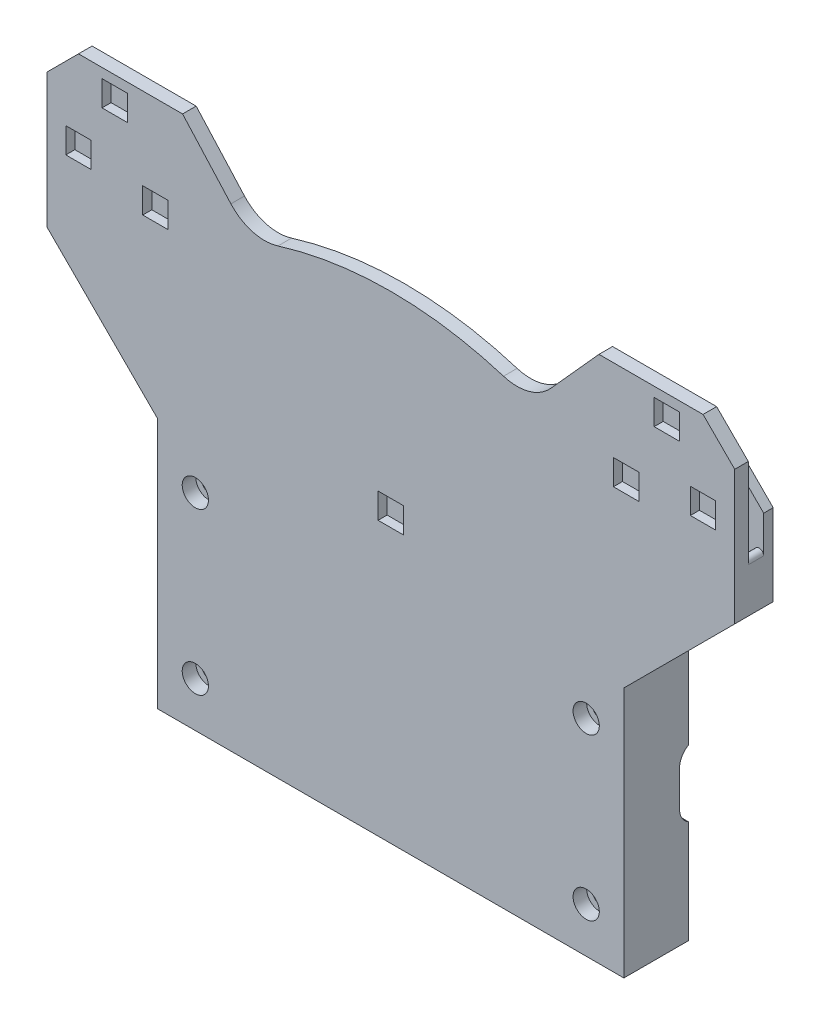
SolidWorks part; units mm, degrees
ref_plane "Front Plane" through (0, 0, 0) normal (0, 0, 1) x (1, 0, 0)
ref_plane "Top Plane" through (0, 0, 0) normal (0, 1, 0) x (1, 0, 0)
ref_plane "Right Plane" through (0, 0, 0) normal (1, 0, 0) x (0, 0, -1)
sketch "Sketch1" plane through (0, 0, 0) normal (0, 0, 1) x (1, 0, 0)
  circle A0 centre (43.18, -17.78) radius 3.5
  circle A1 centre (43.18, -17.78) radius 1.5 construction
  circle A2 centre (43.18, -17.78) radius 1.5
  circle A3 centre (43.18, 17.78) radius 1.5 construction
  circle A4 centre (-43.18, 17.78) radius 1.5 construction
  circle A5 centre (-43.18, -17.78) radius 1.5 construction
  circle A6 centre (43.18, 17.78) radius 1.5
  circle A7 centre (-43.18, 17.78) radius 1.5
  circle A8 centre (-43.18, -17.78) radius 1.5
  circle A9 centre (43.18, 17.78) radius 3.5
  circle A10 centre (-43.18, -17.78) radius 3.5
  circle A11 centre (-43.18, 17.78) radius 3.5
  dimension "D1" = 7
extrude "Boss-Extrude1" add sketch "Sketch1" along normal blind 5
sketch "Sketch2" plane through (0, 0, 5) normal (0, 0, 1) x (1, 0, 0)
  line L9 (-51.5, 27.75) -> (-51.5, -27.75)
  line L10 (-51.5, -27.75) -> (51.5, -27.75)
  line L11 (51.5, -27.75) -> (51.5, 27.75)
  line L12 (51.5, 27.75) -> (-51.5, 27.75)
  line L13 (-51.5, 27.75) -> (-51.5, -27.75)
  line L14 (-51.5, -27.75) -> (51.5, -27.75)
  line L15 (51.5, -27.75) -> (51.5, 27.75)
  line L16 (51.5, 27.75) -> (-51.5, 27.75)
  circle A0 centre (43.18, -17.78) radius 1.5 construction
  circle A1 centre (43.18, -17.78) radius 1.5
  circle A2 centre (-43.18, -17.78) radius 1.5 construction
  circle A3 centre (-43.18, -17.78) radius 1.5
  circle A4 centre (43.18, 17.78) radius 1.5 construction
  circle A5 centre (43.18, 17.78) radius 1.5
  circle A6 centre (-43.18, 17.78) radius 1.5 construction
  circle A7 centre (-43.18, 17.78) radius 1.5
  dimension "D1" = 3
extrude "Boss-Extrude2" add sketch "Sketch2" along normal blind 2
sketch "Sketch4" plane through (0, 0, 7) normal (0, 0, 1) x (1, 0, 0)
  line L0 (76, 68.9071) -> (76, 118.9) construction
  line L1 (76, 68.9071) -> (76, 118.9)
  line L2 (-76, 118.9) -> (-76, 68.9071) construction
  line L3 (-76, 118.9) -> (-76, 68.9071)
  line L4 (76, 68.9071) -> (76, -27.75)
  line L5 (76, -27.75) -> (-76, -27.75)
  line L6 (-76, -27.75) -> (-76, 68.9071)
  line L7 (-51.5, -27.75) -> (51.5, -27.75) construction
  line L8 (76, 88.84) -> (46, 88.84)
  line L9 (46, 88.84) -> (28, 68.84)
  line L10 (0, 0) -> (0, 120.911) construction
  line L11 (-46, 88.84) -> (-28, 68.84)
  line L12 (-76, 88.84) -> (-46, 88.84)
  line L13 (51.5, -27.75) -> (51.5, 27.75) construction
  line L14 (51.5, 27.75) -> (-51.5, 27.75) construction
  line L15 (-51.5, 27.75) -> (-51.5, -27.75) construction
  line L16 (51.5, -27.75) -> (51.5, 27.75)
  line L17 (51.5, 27.75) -> (-51.5, 27.75)
  line L18 (-51.5, 27.75) -> (-51.5, -27.75)
  circle A0 centre (-69, 70.9) radius 1.5 construction
  circle A1 centre (-69, 70.9) radius 1.5
  circle A2 centre (-52, 67.9) radius 1.5 construction
  circle A3 centre (-52, 67.9) radius 1.5
  circle A4 centre (69, 70.9) radius 1.5 construction
  circle A5 centre (69, 70.9) radius 1.5
  circle A6 centre (52, 67.9) radius 1.5 construction
  circle A7 centre (52, 67.9) radius 1.5
  arc A8 (41.0357, 62.5736) -> (-41.0357, 62.5736) centre (0, -6.1) ccw construction
  arc A9 (41.0357, 62.5736) -> (-41.0357, 62.5736) centre (0, -6.1) ccw
  circle A10 centre (61, 83.9) radius 1.5 construction
  circle A11 centre (61, 83.9) radius 1.5
  circle A12 centre (-61, 83.9) radius 1.5 construction
  circle A13 centre (-61, 83.9) radius 1.5
  circle A14 centre (0, 35.482) radius 1.5 construction
  circle A15 centre (0, 35.482) radius 1.5
  dimension "D1" = 30
  dimension "D2" = 20
  dimension "D3" = 18
extrude "Boss-Extrude3" add sketch "Sketch4" against normal up to surface (2 mm away)
sketch "Sketch6" plane through (0, 0, 5) normal (0, 0, -1) x (-1, 0, 0)
  line L0 (49, -25.25) -> (49, 25.25)
  line L1 (49, 25.25) -> (-49, 25.25)
  line L2 (-49, 25.25) -> (-49, -25.25)
  line L3 (-49, -25.25) -> (49, -25.25)
  line L4 (48.5, -24.75) -> (48.5, 24.75)
  line L5 (48.5, 24.75) -> (-48.5, 24.75)
  line L6 (-48.5, 24.75) -> (-48.5, -24.75)
  line L7 (-48.5, -24.75) -> (48.5, -24.75)
  line L8 (48.5, -24.75) -> (48.5, 24.75) construction
  line L9 (48.5, 24.75) -> (-48.5, 24.75) construction
  line L10 (-48.5, 24.75) -> (-48.5, -24.75) construction
  line L11 (-48.5, -24.75) -> (48.5, -24.75) construction
  line L12 (-51.5, -27.75) -> (51.5, -27.75)
  line L13 (51.5, -27.75) -> (51.5, 27.75)
  line L14 (51.5, 27.75) -> (-51.5, 27.75)
  line L15 (-51.5, 27.75) -> (-51.5, -27.75)
  dimension "D1" = 0
  dimension "D2" = 0.5
  dimension "D3" = 2.5
extrude "Boss-Extrude4" add sketch "Sketch6" along normal up to surface (6.6 mm away)
sketch "Sketch7" plane through (0, 0, 5) normal (0, 0, -1) x (-1, 0, 0)
  line L0 (-51.5, 27.75) -> (-76, 52.25)
  line L1 (-76, -27.75) -> (-76, 88.84) construction
  line L2 (-76, 52.25) -> (-76, -27.75)
  line L3 (-76, -27.75) -> (-51.5, -27.75)
  line L4 (-51.5, -27.75) -> (-51.5, 27.75)
  line L5 (51.5, 27.75) -> (76, 52.25)
  line L6 (76, -27.75) -> (76, 88.84) construction
  line L7 (76, 52.25) -> (76, -27.75)
  line L8 (76, -27.75) -> (51.5, -27.75)
  line L9 (51.5, -27.75) -> (51.5, 27.75)
  line L10 (-76, 52.25) -> (76, 52.25) construction
  dimension "D1" = 45
extrude "Cut-Extrude1" cut sketch "Sketch7" against normal blind 10
sketch "Sketch9" plane through (0, 0, 5) normal (0, 0, -1) x (-1, 0, 0)
  line L0 (76.3, 68.9071) -> (76.3, 118.9831)
  line L1 (76.3, 118.9831) -> (70.3, 128.9831)
  line L2 (70.3, 128.9831) -> (70.3, 208.8169)
  line L3 (70.3, 208.8169) -> (76.3, 218.8169)
  line L4 (76.3, 218.8169) -> (76.3, 288.5517)
  line L5 (-76.3, 288.5517) -> (-76.3, 218.8169)
  line L6 (-76.3, 218.8169) -> (-70.3, 208.8169)
  line L7 (-70.3, 208.8169) -> (-70.3, 128.9831)
  line L8 (-70.3, 128.9831) -> (-76.3, 118.9831)
  line L9 (-76.3, 118.9831) -> (-76.3, 68.9071)
  line L10 (76, 68.9071) -> (76, 118.9)
  line L11 (76, 118.9) -> (70, 128.9)
  line L12 (70, 128.9) -> (70, 208.9)
  line L13 (70, 208.9) -> (76, 218.9)
  line L14 (76, 218.9) -> (76, 288.4236)
  line L15 (-76, 288.4236) -> (-76, 218.9)
  line L16 (-76, 218.9) -> (-70, 208.9)
  line L17 (-70, 208.9) -> (-70, 128.9)
  line L18 (-70, 128.9) -> (-76, 118.9)
  line L19 (-76, 118.9) -> (-76, 68.9071)
  line L20 (76, 68.9071) -> (76, 118.9) construction
  line L21 (76, 118.9) -> (70, 128.9) construction
  line L22 (70, 128.9) -> (70, 208.9) construction
  line L23 (70, 208.9) -> (76, 218.9) construction
  line L24 (76, 218.9) -> (76, 288.4236) construction
  line L25 (-76, 288.4236) -> (-76, 218.9) construction
  line L26 (-76, 218.9) -> (-70, 208.9) construction
  line L27 (-70, 208.9) -> (-70, 128.9) construction
  line L28 (-70, 128.9) -> (-76, 118.9) construction
  line L29 (-76, 118.9) -> (-76, 68.9071) construction
  line L39 (-76, 88.84) -> (-76, 52.25)
  line L40 (-76, 52.25) -> (-51.5, 27.75)
  line L41 (-51.5, 27.75) -> (51.5, 27.75)
  line L42 (51.5, 27.75) -> (76, 52.25)
  line L43 (76, 52.25) -> (76, 88.84)
  line L44 (76, 88.84) -> (46, 88.84)
  line L45 (46, 88.84) -> (28, 68.84)
  line L46 (-28, 68.84) -> (-46, 88.84)
  line L47 (-46, 88.84) -> (-76, 88.84)
  line L48 (-76, 88.84) -> (-76, 52.25)
  line L49 (-76, 52.25) -> (-51.5, 27.75)
  line L50 (-51.5, 27.75) -> (51.5, 27.75)
  line L51 (51.5, 27.75) -> (76, 52.25)
  line L52 (76, 52.25) -> (76, 88.84)
  line L53 (76, 88.84) -> (46, 88.84)
  line L54 (46, 88.84) -> (28, 68.84)
  line L55 (-28, 68.84) -> (-46, 88.84)
  line L56 (-46, 88.84) -> (-76, 88.84)
  arc A1 (-66.1471, 58.6082) -> (-40.9121, 62.298) centre (-65, 138.9) ccw
  arc A2 (40.9121, 62.298) -> (-40.9121, 62.298) centre (0, -6.1) ccw
  arc A3 (40.9121, 62.298) -> (66.1471, 58.6082) centre (65, 138.9) ccw
  arc A4 (66.1471, 58.6082) -> (76.3, 68.9071) centre (66, 68.9071) ccw
  arc A5 (76.3, 288.5517) -> (-76.3, 288.5517) centre (0, 208.9) ccw
  arc A6 (-76.3, 68.9071) -> (-66.1471, 58.6082) centre (-66, 68.9071) ccw
  arc A7 (41.0357, 62.5736) -> (-41.0357, 62.5736) centre (0, -6.1) ccw
  arc A8 (41.0357, 62.5736) -> (66.1429, 58.9082) centre (65, 138.9) ccw
  arc A9 (66.1429, 58.9082) -> (76, 68.9071) centre (66, 68.9071) ccw
  arc A10 (76, 288.4236) -> (-76, 288.4236) centre (0, 208.9) ccw
  arc A11 (-76, 68.9071) -> (-66.1429, 58.9082) centre (-66, 68.9071) ccw
  arc A12 (-66.1429, 58.9082) -> (-41.0357, 62.5736) centre (-65, 138.9) ccw
  arc A13 (41.0357, 62.5736) -> (-41.0357, 62.5736) centre (0, -6.1) ccw construction
  arc A14 (41.0357, 62.5736) -> (66.1429, 58.9082) centre (65, 138.9) ccw construction
  arc A15 (66.1429, 58.9082) -> (76, 68.9071) centre (66, 68.9071) ccw construction
  arc A16 (76, 288.4236) -> (-76, 288.4236) centre (0, 208.9) ccw construction
  arc A17 (-76, 68.9071) -> (-66.1429, 58.9082) centre (-66, 68.9071) ccw construction
  arc A18 (-66.1429, 58.9082) -> (-41.0357, 62.5736) centre (-65, 138.9) ccw construction
  circle A19 centre (0, 35.482) radius 1.5 construction
  arc A20 (28, 68.84) -> (-28, 68.84) centre (0, -6.1) ccw
  arc A21 (28, 68.84) -> (-28, 68.84) centre (0, -6.1) ccw
  circle A22 centre (0, 35.482) radius 1.5
  circle M29 centre (0, 35.482) radius 1.5
  line M35 (-76, 52.25) -> (-51.5, 27.75)
  line M36 (-51.5, 27.75) -> (51.5, 27.75)
  line M37 (51.5, 27.75) -> (76, 52.25)
  line M38 (76, 52.25) -> (76, 88.84)
  dimension "D1" = 0
  dimension "D2" = 0.3
  dimension "D3" = 0
extrude "Boss-Extrude5" add sketch "Sketch9" along normal up to surface (3 mm away) contours A6 L48 A4 A3 A2 A1 M35 M36 M37 M38 M29
sketch "Sketch10" plane through (0, 0, 2) normal (0, 0, -1) x (-1, 0, 0)
  line L1 (-5.1061, 39.5578) -> (-4.2, 38.4952)
  line L2 (-4.2, 38.4952) -> (-4.2, 35.482)
  line L3 (4.2, 35.482) -> (4.2, 38.5758)
  line L4 (4.2, 38.5758) -> (5.1906, 39.5664)
  line L5 (-51.5, 27.75) -> (-76, 52.25) construction
  line L6 (-51.5, 27.75) -> (-76, 52.25)
  line L7 (51.5, 27.75) -> (-51.5, 27.75) construction
  line L8 (51.5, 27.75) -> (-51.5, 27.75)
  line L9 (76, 52.25) -> (51.5, 27.75) construction
  line L10 (76, 52.25) -> (51.5, 27.75)
  line L11 (-76, 52.25) -> (-76, 66.4394) construction
  line L12 (-76, 52.25) -> (-76, 66.4394)
  line L13 (76, 66.4394) -> (76, 52.25) construction
  line L14 (76, 66.4394) -> (76, 52.25)
  line L15 (76, 66.4394) -> (76, 77.25)
  line L16 (76, 66.4394) -> (76, 88.84) construction
  line L17 (76, 77.25) -> (-76, 77.25)
  line L18 (-76, 66.4394) -> (-76, 88.84) construction
  line L19 (-76, 77.25) -> (-76, 66.4394)
  line L21 (50.7778, 80.9023) -> (60.602, 79.9199)
  line L22 (61.398, 87.8801) -> (51.4846, 88.8715)
  line L23 (51.4846, 88.8715) -> (50.4999, 90.0749)
  line L24 (26.5818, 132.9378) -> (26.1966, 134.4398)
  line L25 (26.1966, 134.4398) -> (28.693, 139.542)
  line L26 (21.507, 143.058) -> (18.9712, 137.8751)
  line L27 (18.9712, 137.8751) -> (17.5004, 137.3707)
  line L28 (-17.5883, 137.3382) -> (-19.0106, 137.9557)
  line L29 (-19.0106, 137.9557) -> (-21.507, 143.058)
  line L30 (-28.693, 139.542) -> (-26.1571, 134.3592)
  line L31 (-26.1571, 134.3592) -> (-26.6615, 132.8884)
  line L32 (-50.5, 89.9811) -> (-51.5738, 88.8626)
  line L33 (-51.5738, 88.8626) -> (-61.398, 87.8801)
  line L34 (-60.602, 79.9199) -> (-50.6885, 80.9112)
  line L35 (-50.6885, 80.9112) -> (-49.4851, 79.9266)
  line L36 (-5.0061, 39.7487) -> (-4, 38.5689)
  line L37 (-4, 38.5689) -> (-4, 35.482)
  line L38 (4, 35.482) -> (4, 38.6587)
  line L39 (4, 38.6587) -> (5.0995, 39.7581)
  line L40 (49.5037, 80.0185) -> (50.7778, 80.9023)
  line L41 (50.7778, 80.9023) -> (60.602, 79.9199) construction
  line L42 (61.398, 87.8801) -> (51.4846, 88.8715) construction
  line L43 (51.4846, 88.8715) -> (50.4999, 90.0749) construction
  line L44 (26.5818, 132.9378) -> (26.1966, 134.4398) construction
  line L45 (26.1966, 134.4398) -> (28.693, 139.542) construction
  line L46 (21.507, 143.058) -> (18.9712, 137.8751) construction
  line L47 (18.9712, 137.8751) -> (17.5004, 137.3707) construction
  line L48 (-17.5883, 137.3382) -> (-19.0106, 137.9557) construction
  line L49 (-19.0106, 137.9557) -> (-21.507, 143.058) construction
  line L50 (-28.693, 139.542) -> (-26.1571, 134.3592) construction
  line L51 (-26.1571, 134.3592) -> (-26.6615, 132.8884) construction
  line L52 (-50.5, 89.9811) -> (-51.5738, 88.8626) construction
  line L53 (-51.5738, 88.8626) -> (-61.398, 87.8801) construction
  line L54 (-60.602, 79.9199) -> (-50.6885, 80.9112) construction
  line L55 (-50.6885, 80.9112) -> (-49.4851, 79.9266) construction
  line L56 (-5.0061, 39.7487) -> (-4, 38.5689) construction
  line L57 (-4, 38.5689) -> (-4, 35.482) construction
  line L58 (4, 35.482) -> (4, 38.6587) construction
  line L59 (4, 38.6587) -> (5.0995, 39.7581) construction
  line L60 (49.5037, 80.0185) -> (50.7778, 80.9023) construction
  arc A0 (-4, 35.482) -> (4, 35.482) centre (0, 35.482) ccw construction
  arc A1 (-4, 35.482) -> (4, 35.482) centre (0, 35.482) ccw construction
  arc A2 (-4.2, 35.482) -> (4.2, 35.482) centre (0, 35.482) ccw
  arc A3 (-49.6811, 79.8867) -> (-5.1061, 39.5578) centre (0, 90) ccw
  arc A4 (5.1906, 39.5664) -> (49.6998, 79.979) centre (0, 90) ccw
  circle A5 centre (-69, 70.9) radius 1.5 construction
  circle A6 centre (-69, 70.9) radius 1.5
  circle A7 centre (-52, 67.9) radius 1.5 construction
  circle A8 centre (-52, 67.9) radius 1.5
  circle A9 centre (52, 67.9) radius 1.5 construction
  arc A10 (61.398, 87.8801) -> (60.602, 79.9199) centre (61, 83.9) ccw
  arc A11 (50.4999, 90.0749) -> (26.5818, 132.9378) centre (0, 90) ccw
  arc A12 (21.507, 143.058) -> (28.693, 139.542) centre (25.1, 141.3) ccw
  arc A13 (17.5004, 137.3707) -> (-17.5883, 137.3382) centre (0, 90) ccw
  arc A14 (-28.693, 139.542) -> (-21.507, 143.058) centre (-25.1, 141.3) ccw
  arc A15 (-26.6615, 132.8884) -> (-50.5, 89.9811) centre (0, 90) ccw
  arc A16 (-60.602, 79.9199) -> (-61.398, 87.8801) centre (-61, 83.9) ccw
  arc A17 (-49.4851, 79.9266) -> (-5.0061, 39.7487) centre (0, 90) ccw
  arc A18 (4, 35.482) -> (-4, 35.482) centre (0, 35.482) ccw
  arc A19 (5.0995, 39.7581) -> (49.5037, 80.0185) centre (0, 90) ccw
  arc A20 (61.398, 87.8801) -> (60.602, 79.9199) centre (61, 83.9) ccw construction
  arc A21 (50.4999, 90.0749) -> (26.5818, 132.9378) centre (0, 90) ccw construction
  arc A22 (21.507, 143.058) -> (28.693, 139.542) centre (25.1, 141.3) ccw construction
  arc A23 (17.5004, 137.3707) -> (-17.5883, 137.3382) centre (0, 90) ccw construction
  arc A24 (-28.693, 139.542) -> (-21.507, 143.058) centre (-25.1, 141.3) ccw construction
  arc A25 (-26.6615, 132.8884) -> (-50.5, 89.9811) centre (0, 90) ccw construction
  arc A26 (-60.602, 79.9199) -> (-61.398, 87.8801) centre (-61, 83.9) ccw construction
  arc A27 (-49.4851, 79.9266) -> (-5.0061, 39.7487) centre (0, 90) ccw construction
  arc A28 (4, 35.482) -> (-4, 35.482) centre (0, 35.482) ccw construction
  arc A29 (5.0995, 39.7581) -> (49.5037, 80.0185) centre (0, 90) ccw construction
  circle A30 centre (52, 67.9) radius 1.5
  circle A31 centre (69, 70.9) radius 1.5 construction
  circle A32 centre (69, 70.9) radius 1.5
  arc M32 (-66.1471, 58.6082) -> (-76, 66.4394) centre (-66, 68.9071) cw
  line M33 (-76, 66.4394) -> (-76, 52.25)
  line M34 (-76, 52.25) -> (-51.5, 27.75)
  line M35 (-51.5, 27.75) -> (51.5, 27.75)
  line M36 (51.5, 27.75) -> (76, 52.25)
  line M37 (76, 52.25) -> (76, 66.4394)
  arc M38 (76, 66.4394) -> (66.1471, 58.6082) centre (66, 68.9071) cw
  arc M39 (66.1471, 58.6082) -> (40.9121, 62.298) centre (65, 138.9) cw
  arc M41 (-40.9121, 62.298) -> (-66.1471, 58.6082) centre (-65, 138.9) cw
  dimension "D3" = 25
  dimension "D1" = 0
  dimension "D2" = 0.2
extrude "Boss-Extrude6" add sketch "Sketch10" along normal blind 2.5 contours A4 L4 L3 A2 L2 L1 A3 M41 M32 M33 M34 M35 M36 M37 M38 M39 | A3 L17 L19 M32 M41 | A4 L15 L17 M39 M38
sketch "Sketch11" plane through (0, 0, 7) normal (0, 0, 1) x (1, 0, 0)
  line L11 (51.5, -27.75) -> (51.5, 27.75)
  line L12 (51.5, 27.75) -> (76, 52.25)
  line L13 (76, 52.25) -> (76, 88.84)
  line L14 (76, 88.84) -> (46, 88.84)
  line L15 (46, 88.84) -> (28, 68.84)
  line L16 (-28, 68.84) -> (-46, 88.84)
  line L17 (-46, 88.84) -> (-76, 88.84)
  line L18 (-76, 88.84) -> (-76, 52.25)
  line L19 (-76, 52.25) -> (-51.5, 27.75)
  line L20 (-51.5, 27.75) -> (-51.5, -27.75)
  line L21 (-51.5, -27.75) -> (51.5, -27.75)
  line L22 (51.5, -27.75) -> (51.5, 27.75)
  line L23 (51.5, 27.75) -> (76, 52.25)
  line L24 (76, 52.25) -> (76, 88.84)
  line L25 (76, 88.84) -> (46, 88.84)
  line L26 (46, 88.84) -> (28, 68.84)
  line L27 (-28, 68.84) -> (-46, 88.84)
  line L28 (-46, 88.84) -> (-76, 88.84)
  line L29 (-76, 88.84) -> (-76, 52.25)
  line L30 (-76, 52.25) -> (-51.5, 27.75)
  line L31 (-51.5, 27.75) -> (-51.5, -27.75)
  line L32 (-51.5, -27.75) -> (51.5, -27.75)
  circle A0 centre (43.18, -17.78) radius 1.5 construction
  arc A1 (28, 68.84) -> (-28, 68.84) centre (0, -6.1) ccw
  arc A2 (28, 68.84) -> (-28, 68.84) centre (0, -6.1) ccw
  circle A3 centre (-43.18, -17.78) radius 1.5 construction
  circle A4 centre (-43.18, 17.78) radius 1.5 construction
  circle A5 centre (0, 35.482) radius 1.5 construction
  circle A6 centre (43.18, 17.78) radius 1.5 construction
  circle A7 centre (61, 83.9) radius 1.5 construction
  circle A8 centre (69, 70.9) radius 1.5 construction
  circle A9 centre (52, 67.9) radius 1.5 construction
  circle A10 centre (-61, 83.9) radius 1.5 construction
  circle A11 centre (-69, 70.9) radius 1.5 construction
  circle A12 centre (-52, 67.9) radius 1.5 construction
  circle A13 centre (43.18, -17.78) radius 1.5
  circle A14 centre (-43.18, -17.78) radius 1.5
  circle A15 centre (-43.18, 17.78) radius 1.5
  circle A16 centre (0, 35.482) radius 1.5
  circle A17 centre (43.18, 17.78) radius 1.5
  circle A18 centre (61, 83.9) radius 1.5
  circle A19 centre (69, 70.9) radius 1.5
  circle A20 centre (52, 67.9) radius 1.5
  circle A21 centre (-61, 83.9) radius 1.5
  circle A22 centre (-69, 70.9) radius 1.5
  circle A23 centre (-52, 67.9) radius 1.5
  dimension "D1" = 0
extrude "Boss-Extrude7" add sketch "Sketch11" along normal blind 1
sketch "Sketch13" plane through (0, 0, -1.6) normal (0, 0, -1) x (-1, 0, 0)
  line L0 (-51.5, 27.75) -> (51.5, 27.75) construction
  line L1 (51.5, -27.75) -> (49, -27.75)
  line L2 (51.5, -27.75) -> (51.5, 27.75)
  line L3 (51.5, 27.75) -> (49, 27.75)
  line L4 (49, -27.75) -> (49, 27.75)
  line L5 (49, 25.25) -> (49, -25.25) construction
extrude "Boss-Extrude8" add sketch "Sketch13" along normal blind 11.5
sketch "Sketch14" plane through (0, 0, -1.6) normal (0, 0, -1) x (-1, 0, 0)
  line L0 (-51.5, 27.75) -> (49, 27.75) construction
  line L1 (-51.5, -27.75) -> (-49, -27.75)
  line L2 (-51.5, -27.75) -> (-51.5, 27.75)
  line L3 (-51.5, 27.75) -> (-49, 27.75)
  line L4 (-49, -27.75) -> (-49, 27.75)
  line L5 (-49, -25.25) -> (-49, 25.25) construction
extrude "Boss-Extrude9" add sketch "Sketch14" along normal up to surface (4.7 mm away)
sketch "Sketch15" plane through (0, 0, -1.6) normal (0, 0, -1) x (-1, 0, 0)
  line L1 (-49, -27.75) -> (49, -27.75)
  line L2 (-49, -27.75) -> (-49, -25.25)
  line L3 (-49, -25.25) -> (49, -25.25)
  line L4 (49, -27.75) -> (49, -25.25)
extrude "Boss-Extrude10" add sketch "Sketch15" along normal up to surface (4.7 mm away) up to face at (50.25, 0, -6.3)
sketch "Sketch16" plane through (0, 27.75, 0) normal (0, 1, 0) x (1, 0, 0)
  line L0 (-49, 13.1) -> (-36, 13.1)
  line L1 (-36, 13.1) -> (-24.5, 1.6)
  line L2 (49, 1.6) -> (-49, 1.6) construction
  line L3 (-24.5, 1.6) -> (-49, 1.6)
  line L4 (-49, 1.6) -> (-49, 13.1)
  line L5 (49, 6.3) -> (27.7, 6.3)
  line L6 (-49, 6.3) -> (49, 6.3) construction
  line L7 (27.7, 6.3) -> (23, 1.6)
  line L8 (23, 1.6) -> (49, 1.6)
  line L9 (49, 1.6) -> (49, 6.3)
  line L11 (-25, 11.1) -> (-23.5248, 1.8349) construction
  line L12 (22, 11.1) -> (22, 1.6) construction
  dimension "D1" = 1
  dimension "D2" = 45
  dimension "D3" = 1
  dimension "D4" = 45
extrude "Boss-Extrude11" add sketch "Sketch16" against normal up to surface (2.5 mm away) up to face at (0, 25.25, 1.7)
sketch "Sketch17" plane through (0, 0, 8) normal (0, 0, 1) x (1, 0, 0)
  circle A0 centre (-43.18, 17.78) radius 2.9
  circle A1 centre (-43.18, -17.78) radius 2.9
  circle A2 centre (43.18, -17.78) radius 2.9
  circle A3 centre (43.18, 17.78) radius 2.9
  dimension "D1" = 5.8
extrude "Cut-Extrude2" cut sketch "Sketch17" against normal blind 3
sketch "Sketch18" plane through (0, -27.75, 0) normal (0, -1, 0) x (1, 0, 0)
  line L0 (-49, -13.1) -> (-36, -13.1)
  line L1 (-36, -13.1) -> (-29.2, -6.3)
  line L2 (51.5, -6.3) -> (-49, -6.3) construction
  line L3 (-24.5, -1.6) -> (-36, -13.1) construction
  line L4 (-29.2, -6.3) -> (-49, -6.3)
  line L5 (-49, -6.3) -> (-49, -13.1)
extrude "Boss-Extrude12" add sketch "Sketch18" against normal up to surface (2.5 mm away) up to face at (0, -25.25, -0.65)
chamfer "Chamfer1" distance 7 angle 45 4 edges at (-76, 88.84, 6.5) (-76, 77.25, 0.75) (76, 77.25, 0.75) (76, 88.84, 6.5)
sketch "Sketch19" plane through (0, 0, 8) normal (0, 0, 1) x (1, 0, 0)
  line L0 (0, 0) -> (0, 86.7) construction
  line L25 (-2.8, 38.282) -> (2.8, 38.282)
  line L26 (-2.8, 38.282) -> (-2.8, 32.682)
  line L27 (-2.8, 32.682) -> (2.8, 32.682)
  line L28 (2.8, 38.282) -> (2.8, 32.682)
  line L29 (-2.8, 38.282) -> (2.8, 32.682) construction
  line L30 (-2.8, 32.682) -> (2.8, 38.282) construction
  line L31 (49.2, 70.7) -> (54.8, 70.7)
  line L32 (49.2, 70.7) -> (49.2, 65.1)
  line L33 (49.2, 65.1) -> (54.8, 65.1)
  line L34 (54.8, 70.7) -> (54.8, 65.1)
  line L35 (49.2, 70.7) -> (54.8, 65.1) construction
  line L36 (49.2, 65.1) -> (54.8, 70.7) construction
  line L37 (66.2, 73.7) -> (71.8, 73.7)
  line L38 (66.2, 73.7) -> (66.2, 68.1)
  line L39 (66.2, 68.1) -> (71.8, 68.1)
  line L40 (71.8, 73.7) -> (71.8, 68.1)
  line L41 (66.2, 73.7) -> (71.8, 68.1) construction
  line L42 (66.2, 68.1) -> (71.8, 73.7) construction
  line L43 (58.2, 86.7) -> (63.8, 86.7)
  line L44 (58.2, 86.7) -> (58.2, 81.1)
  line L45 (58.2, 81.1) -> (63.8, 81.1)
  line L46 (63.8, 86.7) -> (63.8, 81.1)
  line L47 (58.2, 86.7) -> (63.8, 81.1) construction
  line L48 (58.2, 81.1) -> (63.8, 86.7) construction
  line L49 (-58.2, 81.1) -> (-63.8, 86.7) construction
  line L50 (-58.2, 86.7) -> (-63.8, 81.1) construction
  line L51 (-66.2, 68.1) -> (-71.8, 73.7) construction
  line L52 (-66.2, 73.7) -> (-71.8, 68.1) construction
  line L53 (-49.2, 65.1) -> (-54.8, 70.7) construction
  line L54 (-49.2, 70.7) -> (-54.8, 65.1) construction
  line L55 (-63.8, 86.7) -> (-63.8, 81.1)
  line L56 (-58.2, 81.1) -> (-63.8, 81.1)
  line L57 (-58.2, 86.7) -> (-58.2, 81.1)
  line L58 (-58.2, 86.7) -> (-63.8, 86.7)
  line L59 (-71.8, 73.7) -> (-71.8, 68.1)
  line L60 (-66.2, 68.1) -> (-71.8, 68.1)
  line L61 (-66.2, 73.7) -> (-66.2, 68.1)
  line L62 (-66.2, 73.7) -> (-71.8, 73.7)
  line L63 (-54.8, 70.7) -> (-54.8, 65.1)
  line L64 (-49.2, 65.1) -> (-54.8, 65.1)
  line L65 (-49.2, 70.7) -> (-49.2, 65.1)
  line L66 (-49.2, 70.7) -> (-54.8, 70.7)
  point P0 (0, 35.482)
  point P5 (52, 67.9)
  point P11 (69, 70.9)
  point P16 (61, 83.9)
  point P38 (-61, 83.9)
  point P39 (-69, 70.9)
  point P40 (-52, 67.9)
  dimension "D1" = 5.6
extrude "Cut-Extrude3" cut sketch "Sketch19" against normal blind 2
sketch "Sketch20" plane through (0, 0, 6) normal (0, 0, 1) x (1, 0, 0)
  circle A0 centre (-61, 83.9) radius 1.5 construction
  circle A1 centre (-61, 83.9) radius 1.5
  circle A2 centre (-69, 70.9) radius 1.5 construction
  circle A3 centre (-69, 70.9) radius 1.5
  circle A4 centre (-52, 67.9) radius 1.5 construction
  circle A5 centre (-52, 67.9) radius 1.5
  circle A6 centre (0, 35.482) radius 1.5 construction
  circle A7 centre (0, 35.482) radius 1.5
  circle A8 centre (52, 67.9) radius 1.5 construction
  circle A9 centre (52, 67.9) radius 1.5
  circle A10 centre (69, 70.9) radius 1.5 construction
  circle A11 centre (69, 70.9) radius 1.5
  circle A12 centre (61, 83.9) radius 1.5 construction
  circle A13 centre (61, 83.9) radius 1.5
extrude "Boss-Extrude13" add sketch "Sketch20" against normal blind 0.2
sketch "Sketch21" plane through (0, 0, 5) normal (0, 0, -1) x (-1, 0, 0)
  line L8 (76, 66.4394) -> (76, 81.84)
  line L9 (76, 81.84) -> (69, 88.84)
  line L10 (69, 88.84) -> (46, 88.84)
  line L11 (46, 88.84) -> (28, 68.84)
  line L12 (-28, 68.84) -> (-46, 88.84)
  line L13 (-46, 88.84) -> (-69, 88.84)
  line L14 (-69, 88.84) -> (-76, 81.84)
  line L15 (-76, 81.84) -> (-76, 66.4394)
  line L16 (76, 66.4394) -> (76, 81.84)
  line L17 (76, 81.84) -> (69, 88.84)
  line L18 (69, 88.84) -> (46, 88.84)
  line L19 (46, 88.84) -> (28, 68.84)
  line L20 (-28, 68.84) -> (-46, 88.84)
  line L21 (-46, 88.84) -> (-69, 88.84)
  line L22 (-69, 88.84) -> (-76, 81.84)
  line L23 (-76, 81.84) -> (-76, 66.4394)
  arc A6 (28, 68.84) -> (-28, 68.84) centre (0, -6.1) ccw
  arc A7 (-76, 66.4394) -> (-66.1471, 58.6082) centre (-66, 68.9071) ccw
  arc A8 (-66.1471, 58.6082) -> (-40.9121, 62.298) centre (-65, 138.9) ccw
  arc A9 (40.9121, 62.298) -> (-40.9121, 62.298) centre (0, -6.1) ccw
  arc A10 (40.9121, 62.298) -> (66.1471, 58.6082) centre (65, 138.9) ccw
  arc A11 (66.1471, 58.6082) -> (76, 66.4394) centre (66, 68.9071) ccw
  arc A12 (28, 68.84) -> (-28, 68.84) centre (0, -6.1) ccw
  arc A13 (-76, 66.4394) -> (-66.1471, 58.6082) centre (-66, 68.9071) ccw
  arc A14 (-66.1471, 58.6082) -> (-40.9121, 62.298) centre (-65, 138.9) ccw
  arc A15 (40.9121, 62.298) -> (-40.9121, 62.298) centre (0, -6.1) ccw
  arc A16 (40.9121, 62.298) -> (66.1471, 58.6082) centre (65, 138.9) ccw
  arc A17 (66.1471, 58.6082) -> (76, 66.4394) centre (66, 68.9071) ccw
  dimension "D1" = 0
extrude "Cut-Extrude4" cut sketch "Sketch21" along normal blind 3.4
sketch "Sketch22" plane through (51.5, 0, 0) normal (1, 0, 0) x (0, 0, -1)
  line L0 (-8, -27.75) -> (-8, 27.75) construction
  line L1 (1.6, 27.75) -> (13.1, 27.75) construction
  line L6 (4.3, 6.25) -> (4.3, -1.55)
  line L7 (12.3, -1.55) -> (12.3, 6.25)
  arc A6 (12.3, 6.25) -> (4.3, 6.25) centre (8.3, 6.25) ccw
  arc A7 (4.3, -1.55) -> (12.3, -1.55) centre (8.3, -1.55) ccw
  dimension "D3" = 15.8
  dimension "D1" = 15.8
  dimension "D2" = 8
  dimension "D4" = 8
  dimension "D5" = 16.3
  dimension "D6" = 21.5
extrude "Cut-Extrude5" cut sketch "Sketch22" against normal blind 3.1
chamfer "Chamfer2" distance 2 angle 45 4 edges at (-39.68, 17.78, 5) (-39.68, -17.78, 5) (46.68, 17.78, 5) (46.68, -17.78, 5)
chamfer "Chamfer3" distance 1.5 angle 45 1 edges at (0, 27.75, -0.5)
sketch "Sketch24" plane through (0, 0, -0.5) normal (0, 0, -1) x (-1, 0, 0)
  line L0 (16.4412, 42.2513) -> (13.336, 55.7014) construction
  line L1 (16.4412, 42.2513) -> (13.336, 55.7014) construction
  line L2 (6.1544, 39.8764) -> (3.0492, 53.3265) construction
  line L3 (6.1544, 39.8764) -> (3.0492, 53.3265) construction
  line L4 (16.4412, 42.2513) -> (17.5659, 37.3795)
  line L5 (17.5659, 37.3795) -> (7.2792, 35.0046)
  line L6 (7.2792, 35.0046) -> (6.1544, 39.8764)
  line L7 (6.1544, 39.8764) -> (16.4412, 42.2513)
  dimension "D1" = 5
extrude "Cut-Extrude6" cut sketch "Sketch24" against normal blind 1.5
fillet "Fillet2" radius 1 3 edges at (-17.0262, 39.7174, -0.5) (-12.4226, 36.192, -0.5) (-6.7394, 37.3425, -0.5)
fillet "Fillet3" radius 1 2 edges at (76, 66.4394, 3.3) (-76, 66.4394, 3.3)
chamfer "Chamfer4" distance 1.5 angle 45 2 edges at (-49.0706, 77.25, 0.55) (49.0706, 77.25, 0.55)
sketch "Sketch25" plane through (0, 0, 8) normal (0, 0, 1) x (1, 0, 0)
  line L0 (-28, 68.84) -> (-46, 88.84) construction
  line L1 (-28, 68.84) -> (-46, 88.84)
  line L2 (46, 88.84) -> (28, 68.84) construction
  line L3 (46, 88.84) -> (28, 68.84)
  arc A0 (28, 68.84) -> (-28, 68.84) centre (0, -6.1) ccw construction
  arc A1 (28, 68.84) -> (-28, 68.84) centre (0, -6.1) ccw
  arc A2 (33.4084, 70.9706) -> (-35.4195, 70.0673) centre (0, -6.1) ccw
  arc A3 (29.4, 72.587) -> (-29.4, 72.587) centre (0, -6.1) ccw construction
  arc M45 (28, 68.84) -> (-28, 68.84) centre (0, -6.1) ccw
  line M46 (-28, 68.84) -> (-46, 88.84)
  dimension "D1" = 4
extrude "Boss-Extrude14" add sketch "Sketch25" against normal up to surface (3 mm away) contours L3 A2 M46 M45 up to face at (-50.5, 67.9, 5)
fillet "Fillet4" radius 10 2 edges at (-30.8654, 72.0238, 6.5) (30.8654, 72.0238, 6.5)
sketch "Sketch26" plane through (0, 0, 5) normal (0, 0, -1) x (-1, 0, 0)
  line L0 (-51.5, -5.0141) -> (-51.5, -27.75) construction
  line L1 (-35, -11.95) -> (-28, -11.95)
  line L2 (-35, -11.95) -> (-35, -21.95)
  line L3 (-35, -21.95) -> (-28, -21.95)
  line L4 (-28, -11.95) -> (-28, -21.95)
  line L5 (-6, -11.95) -> (-13, -11.95)
  line L6 (-6, -11.95) -> (-6, -21.95)
  line L7 (-6, -21.95) -> (-13, -21.95)
  line L8 (-13, -11.95) -> (-13, -21.95)
  line L9 (-51.5, -27.75) -> (29.2, -27.75) construction
  dimension "D1" = 10
  dimension "D2" = 15
  dimension "D3" = 7
  dimension "D4" = 16.5
  dimension "D5" = 5.8
extrude "Boss-Extrude15" add sketch "Sketch26" along normal up to surface (5 mm away) separate body up to face at (46.68, -17.78, 0)
sketch "Sketch27" plane through (13, 0, 0) normal (1, 0, 0) x (0, 0, -1)
  line L0 (-3, -11.95) -> (-3, -21.95)
  line L4 (-5, -21.95) -> (0, -21.95)
  line L5 (0, -21.95) -> (0, -11.95)
  line L6 (0, -11.95) -> (-5, -11.95)
  line L7 (-5, -11.95) -> (-5, -21.95)
  line L8 (-5, -21.95) -> (0, -21.95)
  line L9 (0, -21.95) -> (0, -11.95)
  line L10 (0, -11.95) -> (-5, -11.95)
  line L11 (-5, -11.95) -> (-5, -21.95)
  line M6 (-5, -21.95) -> (0, -21.95)
  line M8 (0, -11.95) -> (-5, -11.95)
  line M9 (-5, -11.95) -> (-5, -21.95)
  dimension "D2" = 2
  dimension "D1" = 0
extrude "Boss-Extrude16" add sketch "Sketch27" along normal up to surface (15 mm away) contours L0 M8 M9 M6 up to face at (28, -16.95, 2.5)
ref_plane "Plane1" through (0, 0, -11.1) normal (0, 0, -1) x (-1, 0, 0)
split "Split1" [suppressed] bodies to split 126 123
sketch "Sketch30" plane through (0, 0, -13.1) normal (0, 0, -1) x (-1, 0, 0)
  circle A0 centre (43.5, 1.5) radius 13.3
  dimension "D1" = 26.6
extrude "Cut-Extrude7" cut sketch "Sketch30" against normal blind 1
